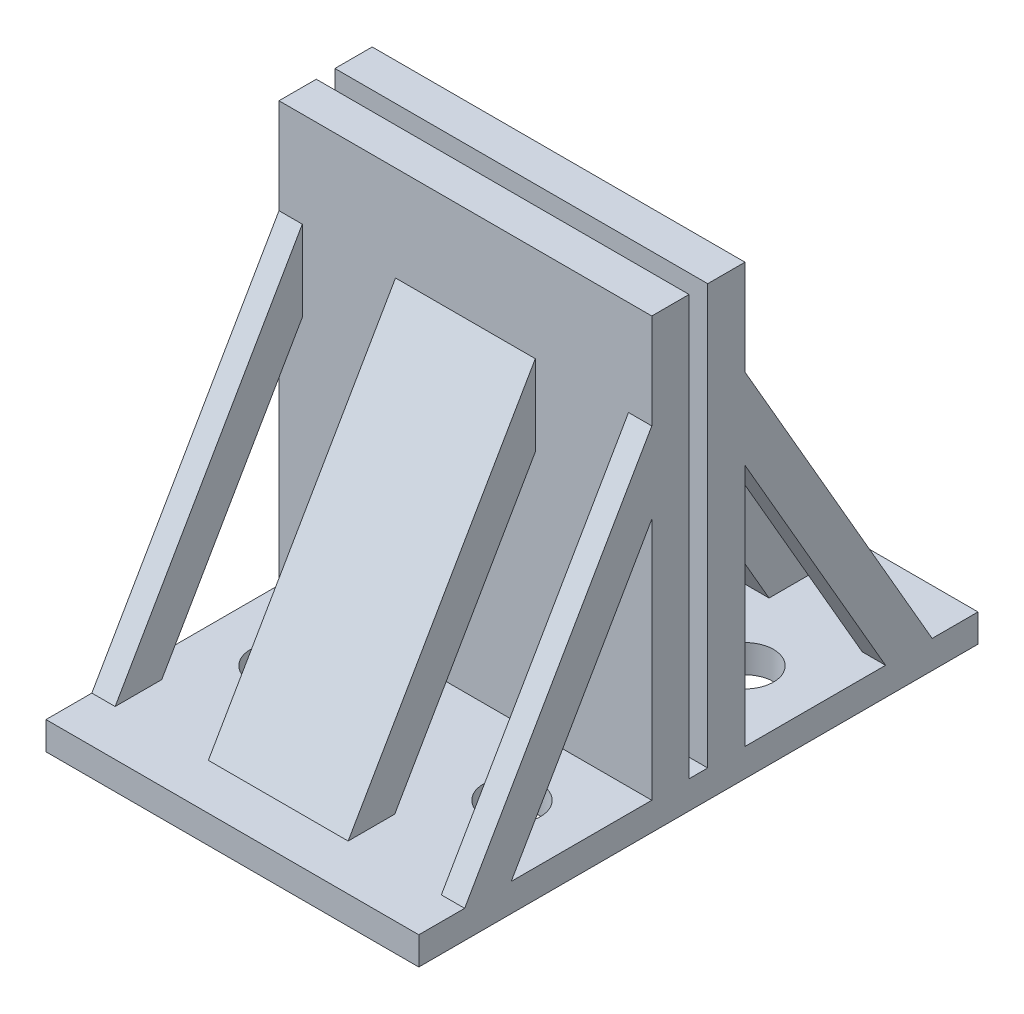
SolidWorks part; units mm, degrees
ref_plane "前视基准面" through (0, 0, 0) normal (0, 0, 1) x (1, 0, 0)
ref_plane "上视基准面" through (0, 0, 0) normal (0, 1, 0) x (1, 0, 0)
ref_plane "右视基准面" through (0, 0, 0) normal (1, 0, 0) x (0, 0, -1)
other "Configuration Table"
sketch "草图1" plane through (0, 0, 0) normal (0, 1, 0) x (1, 0, 0)
  line L0 (-51.8399, 0) -> (43.9443, 0) construction
  line L1 (-20, -30) -> (20, -30)
  line L2 (-20, -30) -> (-20, 30)
  line L3 (-20, 30) -> (20, 30)
  line L4 (20, -30) -> (20, 30)
  line L5 (-20, -30) -> (20, 30) construction
  line L6 (-20, 30) -> (20, -30) construction
  line L7 (0, 42.505) -> (0, -35.4746) construction
  circle A1 centre (-12.5, 12.5) radius 3.05
  circle A2 centre (12.5, 12.5) radius 3.05
  circle A3 centre (12.5, -12.5) radius 3.05
  circle A4 centre (-12.5, -12.5) radius 3.05
  point P0 (0, 0)
  dimension "D3" = 12.5
  dimension "D5" = 6.1
  dimension "D1" = 40
  dimension "D2" = 60
  dimension "D4" = 12.5
extrude "凸台-拉伸1" add sketch "草图1" along normal blind 3
sketch "草图2" plane through (0, 3, 0) normal (0, 1, 0) x (1, 0, 0)
  line L0 (20, -30) -> (20, 30) construction
  line L1 (-20, 1) -> (20, 1)
  line L2 (-20, 1) -> (-20, 5)
  line L3 (-20, 5) -> (20, 5)
  line L4 (20, 1) -> (20, 5)
  line L5 (-20, 1) -> (20, 5) construction
  line L6 (-20, 5) -> (20, 1) construction
  line L7 (-30.4504, 0) -> (41.1328, 0) construction
  line L8 (-20, -5) -> (20, -1) construction
  line L9 (-20, -1) -> (20, -5) construction
  line L10 (20, -1) -> (20, -5)
  line L11 (-20, -5) -> (20, -5)
  line L12 (-20, -1) -> (-20, -5)
  line L13 (-20, -1) -> (20, -1)
  point P0 (0, 3)
  point P14 (0, -3)
  dimension "D1" = 4
  dimension "D2" = 1
extrude "凸台-拉伸2" add sketch "草图2" along normal blind 45
sketch "草图3" plane through (0, 0, 0) normal (1, 0, 0) x (0, 0, -1)
  line L0 (-5, 29.1214) -> (-20.0812, 3)
  line L1 (-20.0812, 3) -> (-25.0812, 3)
  line L2 (-30, 3) -> (-5, 3) construction
  line L3 (-25.0812, 3) -> (-5, 37.7816)
  line L4 (-5, 48) -> (-5, 3) construction
  line L5 (-5, 37.7816) -> (-5, 29.1214)
  line L6 (-9.45, 3) -> (-15.55, 3) construction
  line L7 (0, -6.7591) -> (0, 40.6703) construction
  line L8 (5, 37.7816) -> (5, 29.1214)
  line L9 (25.0812, 3) -> (5, 37.7816)
  line L10 (20.0812, 3) -> (25.0812, 3)
  line L11 (5, 29.1214) -> (20.0812, 3)
  point P2 (-5, 37.1792)
  dimension "D1" = 5
  dimension "D2" = 60
extrude "凸台-拉伸3" add sketch "草图3" against normal blind 20 and the other way blind 20
sketch "草图4" plane through (0, 3, 0) normal (0, 1, 0) x (1, 0, 0)
  line L0 (20, 25.0812) -> (-20, 25.0812) construction
  line L1 (20, -25.0812) -> (-20, -25.0812) construction
  line L2 (20, 5) -> (-20, 5) construction
  line L3 (-20, -5) -> (20, -5) construction
  line L4 (20, 25.0812) -> (-20, 25.0812)
  line L5 (20, -25.0812) -> (-20, -25.0812)
  line L6 (20, 5) -> (-20, 5)
  line L7 (-20, -5) -> (20, -5)
  line L8 (0, -42.1379) -> (0, 35.8881) construction
  line L9 (-17.5, -5) -> (-7.5, -5)
  line L10 (-17.5, -5) -> (-17.5, -25.0812)
  line L11 (-17.5, -25.0812) -> (-7.5, -25.0812)
  line L12 (-7.5, -5) -> (-7.5, -25.0812)
  line L13 (-43.1988, 0) -> (63.4545, 0) construction
  line L14 (-7.5, 5) -> (-7.5, 25.0812)
  line L15 (-17.5, 5) -> (-17.5, 25.0812)
  line L16 (17.5, -5) -> (17.5, -25.0812)
  line L17 (7.5, -5) -> (7.5, -25.0812)
  line L18 (7.5, 5) -> (7.5, 25.0812)
  line L19 (17.5, 5) -> (17.5, 25.0812)
  circle A0 centre (-12.5, -12.5) radius 3.05 construction
  circle A1 centre (-12.5, -12.5) radius 3.05
  circle A2 centre (12.5, -12.5) radius 3.05 construction
  circle A3 centre (12.5, -12.5) radius 3.05
  point P18 (-12.5, -5)
  circle M6 centre (-12.5, -12.5) radius 3.05
  circle M7 centre (12.5, -12.5) radius 3.05
  line M8 (-20, -20.0812) -> (20, -20.0812)
  dimension "D1" = 10
extrude "切除-拉伸1" cut sketch "草图4" along normal through all contours L7 L17 L16 M8 M7 | M7 | L17 L5 L16 M8 | L12 L7 L10 M8 M6 | M6 | L12 L10 L5 M8 | L15 L6 L14 L4 | L6 L19 L4 L18 region at (12.5, 3, -15.0406) region at (-12.5, 3, -15.0406) region at (12.5, 3, 22.5812) region at (12.5, 3, 19.9002) region at (-12.5, 3, 22.5812) region at (-12.5, 3, 19.9002) region at (-12.5, 3, 12.5) region at (12.5, 3, 12.5)
